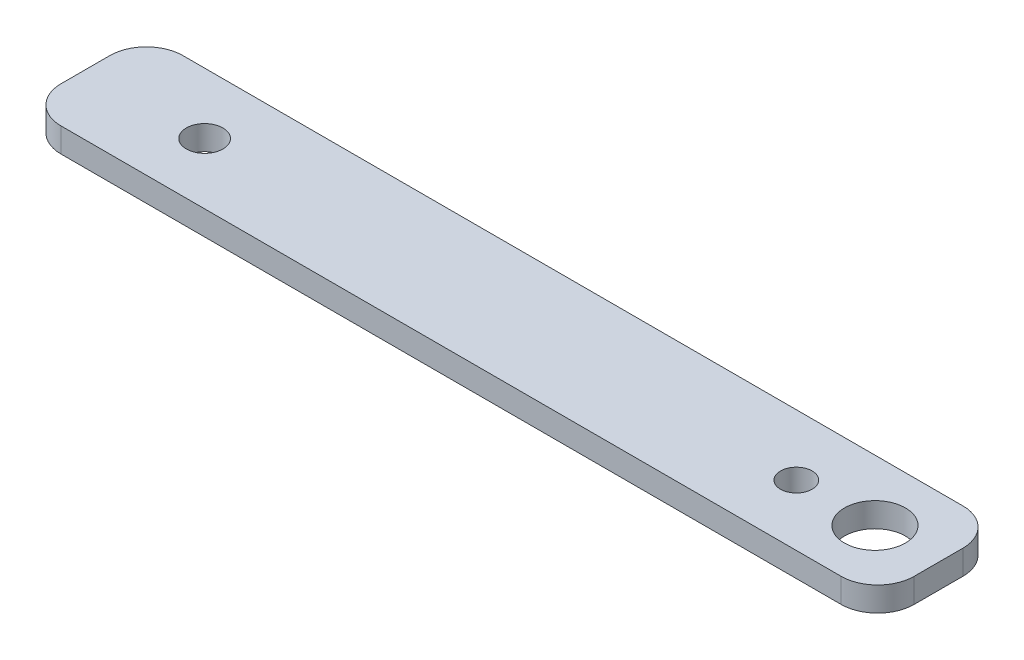
SolidWorks part; units mm, degrees
ref_plane "Front Plane" through (0, 0, 0) normal (0, 0, 1) x (1, 0, 0)
ref_plane "Top Plane" through (0, 0, 0) normal (0, 1, 0) x (1, 0, 0)
ref_plane "Right Plane" through (0, 0, 0) normal (1, 0, 0) x (0, 0, -1)
sketch "Sketch1" plane through (0, 0, 0) normal (0, 1, 0) x (1, 0, 0)
  line L1 (-35, 5) -> (35, 5)
  line L2 (-35, 5) -> (-35, -5)
  line L3 (-35, -5) -> (35, -5)
  line L4 (35, 5) -> (35, -5)
  line L5 (-35, 5) -> (35, -5) construction
  line L6 (-35, -5) -> (35, 5) construction
  point P0 (0, 0)
  dimension "D1" = 10
  dimension "D2" = 70
extrude "Boss-Extrude1" add sketch "Sketch1" along normal blind 2
hole_wizard "Ø5.0mm Dowel Hole1" positions "Sketch5" profile "Sketch6" hole size "Ø5.0" standard "ISO" end condition through all
sketch "Sketch5" plane through (0, 2, 0) normal (0, 1, 0) x (1, 0, 0)
  point P0 (29.7797, 0)
  point P8 (29.7797, 0)
sketch "Sketch6" plane through (29.7797, 2, 0) normal (1, 0, 0) x (0, 0, 1)
  line L0 (0, 0) -> (0, 2)
  line L1 (0, 2) -> (2.5, 2)
  line L2 (2.5, 2) -> (2.5, 0)
  line L5 (2.5, 0) -> (0, 0)
  line L11 (0, -6.35) -> (0, 107.95) construction
  dimension "Thru Hole Dia." = 5
  dimension "Thru Hole Depth" = 2
hole_wizard "Ø3.0mm Dowel Hole1" positions "Sketch3" profile "Sketch4" hole size "Ø3.0" standard "ISO" end condition through all
sketch "Sketch3" plane through (0, 2, 0) normal (0, 1, 0) x (1, 0, 0)
  circle A0 centre (29.7797, 0) radius 2.5 construction
  point P0 (-25.2203, 0)
  dimension "D1" = 55
sketch "Sketch4" plane through (-25.2203, 2, 0) normal (1, 0, 0) x (0, 0, 1)
  line L0 (0, 0) -> (0, 2)
  line L1 (0, 2) -> (1.5, 2)
  line L2 (1.5, 2) -> (1.5, 0)
  line L5 (1.5, 0) -> (0, 0)
  line L11 (0, -6.35) -> (0, 107.95) construction
  dimension "Thru Hole Dia." = 3
  dimension "Thru Hole Depth" = 2
sketch "Sketch2" plane through (0, 2, 0) normal (0, 1, 0) x (1, 0, 0)
  line L0 (29.7797, 5) -> (29.7797, -5) construction
  line L1 (-35, -5) -> (35, -5) construction
  line L3 (35, 0) -> (-35, 0) construction
  line L4 (35, -5) -> (35, 5) construction
  line L5 (-35, 5) -> (-35, -5) construction
  circle A3 centre (23.3297, 0) radius 1.3
  point P4 (0, 0)
  point P5 (24.4139, 0)
  point P10 (29.7797, 0)
  point P11 (0, 0)
  point P12 (24.4139, -5)
  dimension "D1" = 2.6
  dimension "D2" = 6.45
extrude "Cut-Extrude1" cut sketch "Sketch2" against normal blind 3
fillet "Fillet1" radius 3 4 edges at (35, 1, 5) (35, 1, -5) (-35, 1, -5) (-35, 1, 5)
equation "\"globalength1\"=55"
